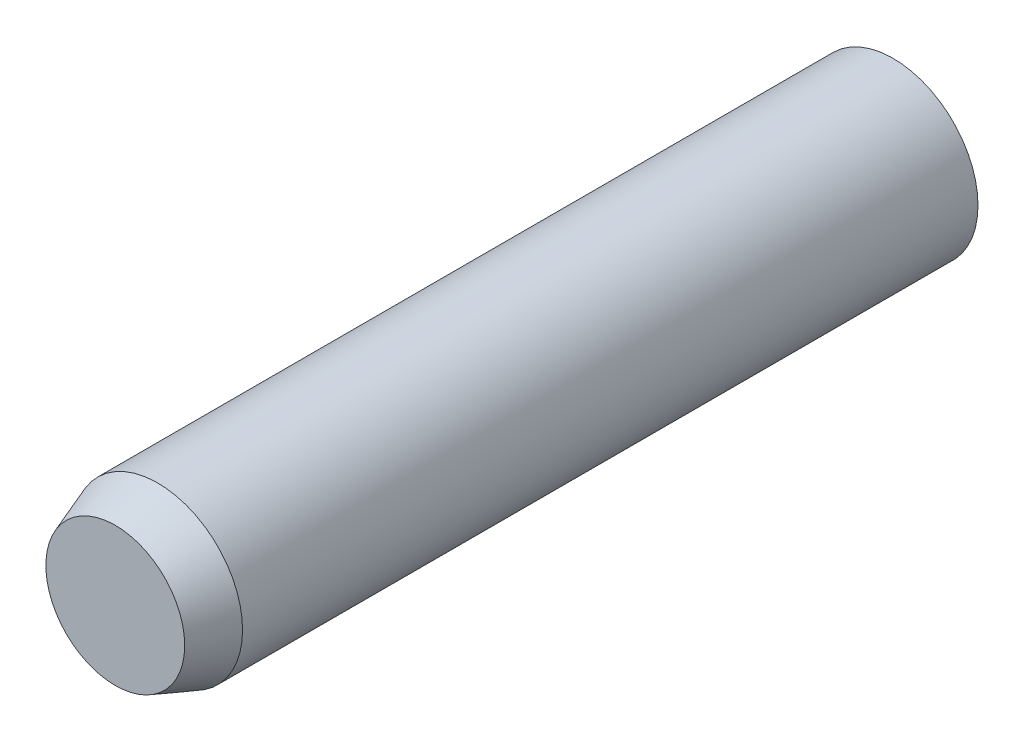
SolidWorks part; units mm, degrees
ref_plane "Front Plane" through (0, 0, 0) normal (0, 0, 1) x (1, 0, 0)
ref_plane "Top Plane" through (0, 0, 0) normal (0, 1, 0) x (1, 0, 0)
ref_plane "Right Plane" through (0, 0, 0) normal (1, 0, 0) x (0, 0, -1)
sketch "Sketch1" plane through (0, 0, 0) normal (0, 0, 1) x (1, 0, 0)
  circle A0 centre (0, 0) radius 6
  dimension "D1" = 12
extrude "Boss-Extrude1" add sketch "Sketch1" along normal blind 55
chamfer "Chamfer1" distance 3 angle 20 1 edges at (6, 0, 55) first distance on face at (6, 0, 55)
